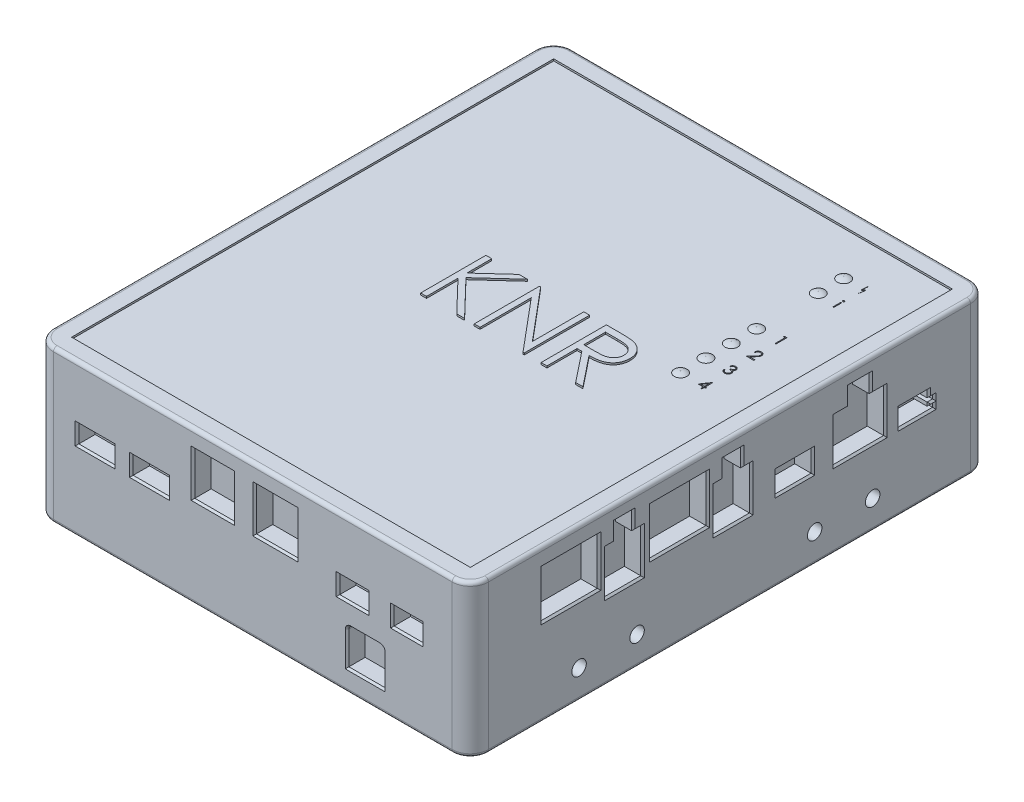
SolidWorks part; units mm, degrees
ref_plane "前基準面" through (0, 0, 0) normal (0, 0, 1) x (1, 0, 0)
ref_plane "上基準面" through (0, 0, 0) normal (0, 1, 0) x (1, 0, 0)
ref_plane "右基準面" through (0, 0, 0) normal (1, 0, 0) x (0, 0, -1)
sketch "草圖1" plane through (0, 0, 0) normal (0, 1, 0) x (1, 0, 0)
  line L1 (0, 0) -> (-120, 0)
  line L2 (0, 0) -> (0, -143)
  line L3 (0, -143) -> (-120, -143)
  line L4 (-120, 0) -> (-120, -143)
  dimension "D1" = 120
  dimension "D2" = 143
extrude "填料-伸長1" add sketch "草圖1" along normal blind 42
fillet "圓角1" radius 5 4 edges at (0, 21, 0) (-120, 21, 0) (-120, 21, 143) (0, 21, 143)
fillet "圓角2" radius 1 16 edges at (-1.4645, 0, 1.4645) (0, 0, 71.5) (-1.4645, 0, 141.5355) (-60, 0, 143) (-118.5355, 0, 141.5355) (-120, 0, 71.5) (-118.5355, 0, 1.4645) (-1.4645, 42, 1.4645) (0, 42, 71.5) (-1.4645, 42, 141.5355) (-60, 42, 143) (-118.5355, 42, 141.5355) (-120, 42, 71.5) (-118.5355, 42, 1.4645) (-60, 0, 0) (-60, 42, 0)
sketch "草圖2" plane through (0, 42, 0) normal (0, 1, 0) x (1, 0, 0)
  line L0 (-115, 0) -> (-5, 0) construction
  line L1 (-115, -5) -> (-5, -5)
  line L2 (-115, -5) -> (-115, -138)
  line L3 (-115, -138) -> (-5, -138)
  line L4 (-5, -5) -> (-5, -138)
  line L5 (-120, -138) -> (-120, -5) construction
  line L6 (0, -5) -> (0, -138) construction
  line L7 (-5, -143) -> (-115, -143) construction
  dimension "D1" = 5
  dimension "D2" = 5
  dimension "D3" = 5
  dimension "D4" = 5
extrude "除料-伸長1" cut sketch "草圖2" against normal blind 0.5
sketch "草圖3" plane through (0, 41.5, 0) normal (0, 1, 0) x (1, 0, 0)
  text T0 "KNR" font "Century Gothic" height 18
extrude "填料-伸長2" add sketch "草圖3" along normal blind 0.5
sketch "草圖4" plane through (0, 41.5, 0) normal (0, 1, 0) x (1, 0, 0)
  line L0 (-5, -138) -> (-5, -5) construction
  line L1 (-5, -5) -> (-115, -5) construction
  circle A0 centre (-23, -17) radius 1.75
  circle A1 centre (-23, -24) radius 1.75
  circle A2 centre (-23, -41) radius 1.75
  circle A3 centre (-23, -48) radius 1.75
  circle A4 centre (-23, -55) radius 1.75
  circle A5 centre (-23, -62) radius 1.75
  dimension "D1" = 18
  dimension "D3" = 3.5
  dimension "D2" = 12
  dimension "D4" = 2
  dimension "D5" = 2
  dimension "D6" = 4
extrude "填料-伸長3" add sketch "草圖4" along normal blind 0.5
fillet "圓角3" radius 3 6 edges at (-23, 42, 18.75) (-23, 42, 63.75) (-23, 42, 56.75) (-23, 42, 49.75) (-23, 42, 42.75) (-23, 42, 25.75)
sketch "草圖6" plane through (0, 41.5, 0) normal (0, 1, 0) x (1, 0, 0)
  circle A0 centre (-23, -17) radius 0.0917 construction
  circle A2 centre (-23, -41) radius 0.0917 construction
  text T0 "ㄣ" font "Century Gothic" height 3
  text T1 "i" font "Century Gothic" height 3
  text T2 "1\r\n2\r\n3\r\n4" font "Century Gothic" height 3
  dimension "D2" = 5
  dimension "D1" = 5
extrude "除料-伸長2" cut sketch "草圖6" against normal blind 0.5
sketch "草圖7" plane through (0, 0, 0) normal (1, 0, 0) x (0, 0, -1)
  line L0 (-143, 1) -> (-143, 41) construction
  line L1 (-123, 37) -> (-107.5, 37)
  line L2 (-123, 37) -> (-123, 24)
  line L3 (-123, 24) -> (-107.5, 24)
  line L4 (-107.5, 37) -> (-107.5, 24)
  line L5 (-138, 42) -> (-5, 42) construction
  line L6 (-105.5, 33) -> (-105.5, 21)
  line L7 (-105.5, 21) -> (-95.5, 21)
  line L8 (-95.5, 21) -> (-95.5, 33)
  line L9 (-95.5, 33) -> (-98, 33)
  line L10 (-98, 33) -> (-98, 38)
  line L11 (-98, 38) -> (-103, 38)
  line L12 (-103, 38) -> (-103, 33)
  line L13 (-103, 33) -> (-105.5, 33)
  line L14 (-93, 24) -> (-77.5, 24)
  line L15 (-93, 37) -> (-93, 24)
  line L16 (-93, 37) -> (-77.5, 37)
  line L17 (-77.5, 37) -> (-77.5, 24)
  line L18 (-75.5, 33) -> (-75.5, 21)
  line L19 (-73, 33) -> (-75.5, 33)
  line L20 (-73, 38) -> (-73, 33)
  line L21 (-68, 38) -> (-73, 38)
  line L22 (-68, 33) -> (-68, 38)
  line L23 (-65.5, 33) -> (-68, 33)
  line L24 (-65.5, 21) -> (-65.5, 33)
  line L25 (-75.5, 21) -> (-65.5, 21)
  line L26 (-42.5, 21) -> (-42.5, 33)
  line L27 (-58.5, 28) -> (-48.5, 28)
  line L28 (-58.5, 28) -> (-58.5, 22)
  line L29 (-58.5, 22) -> (-48.5, 22)
  line L30 (-48.5, 28) -> (-48.5, 22)
  line L31 (-42.5, 33) -> (-38.5, 33)
  line L32 (-38.5, 33) -> (-38.5, 38)
  line L33 (-38.5, 38) -> (-32.5, 38)
  line L34 (-32.5, 38) -> (-32.5, 33)
  line L35 (-32.5, 33) -> (-28.5, 33)
  line L36 (-28.5, 33) -> (-28.5, 21)
  line L37 (-28.5, 21) -> (-42.5, 21)
  line L38 (-16.5, 21) -> (-15, 21)
  line L39 (-24.5, 26) -> (-16.5, 26)
  line L40 (-24.5, 26) -> (-24.5, 21)
  line L41 (-24.5, 21) -> (-16.5, 21)
  line L42 (-16.5, 26) -> (-16.5, 24)
  line L43 (-15, 21) -> (-15, 22)
  line L44 (-15, 22) -> (-16.5, 22)
  line L45 (-15, 24) -> (-16.5, 24)
  line L46 (-15, 23) -> (-15, 24)
  line L47 (-16.5, 23) -> (-15, 23)
  line L48 (-16.5, 23) -> (-16.5, 22)
  dimension "D1" = 20
  dimension "D2" = 5
  dimension "D3" = 13
  dimension "D4" = 15.5
  dimension "D5" = 2
  dimension "D6" = 4
  dimension "D7" = 9
  dimension "D8" = 4.5
  dimension "D9" = 5
  dimension "D10" = 10
  dimension "D11" = 21
  dimension "D12" = 2
  dimension "D13" = 7
  dimension "D14" = 20
  dimension "D15" = 6
  dimension "D16" = 10
  dimension "D17" = 6
  dimension "D18" = 4
  dimension "D19" = 4
  dimension "D20" = 14
  dimension "D21" = 4
  dimension "D22" = 1.5
  dimension "D23" = 1
  dimension "D24" = 8
  dimension "D25" = 5
  dimension "D26" = 2
extrude "除料-伸長3" cut sketch "草圖7" against normal blind 5
chamfer "導角1" distance 0.5 angle 45 46 edges at (0, 26, 20.5) (0, 23.5, 24.5) (0, 25, 16.5) (0, 24, 15.75) (0, 23.5, 15) (0, 23, 15.75) (0, 22.5, 16.5) (0, 22, 15.75) (0, 21.5, 15) (0, 21, 19.75) (0, 21, 35.5) (0, 27, 28.5) (0, 33, 30.5) (0, 35.5, 32.5) (0, 38, 35.5) (0, 35.5, 38.5) (0, 33, 40.5) (0, 27, 42.5) (0, 22, 53.5) (0, 25, 48.5) (0, 28, 53.5) (0, 25, 58.5) (0, 21, 70.5) (0, 27, 65.5) (0, 33, 66.75) (0, 35.5, 68) (0, 38, 70.5) (0, 35.5, 73) (0, 27, 75.5) (0, 33, 74.25) (0, 24, 85.25) (0, 30.5, 77.5) (0, 37, 85.25) (0, 30.5, 93) (0, 33, 96.75) (0, 27, 95.5) (0, 21, 100.5) (0, 35.5, 98) (0, 38, 100.5) (0, 35.5, 103) (0, 33, 104.25) (0, 27, 105.5) (0, 24, 115.25) (0, 30.5, 107.5) (0, 30.5, 123) (0, 37, 115.25)
sketch "草圖8" plane through (0, 0, 0) normal (0, 0, -1) x (-1, 0, 0)
  line L0 (0, 1) -> (0, 41) construction
  line L1 (26, 14) -> (39, 14)
  line L2 (26, 14) -> (26, 8)
  line L3 (26, 8) -> (39, 8)
  line L4 (39, 14) -> (39, 8)
  line L5 (115, 0) -> (5, 0) construction
  line L6 (120, 41) -> (120, 1) construction
  line L7 (23, 25.5) -> (34, 25.5)
  line L8 (23, 25.5) -> (23, 22)
  line L9 (23, 22) -> (34, 22)
  line L10 (34, 25.5) -> (34, 22)
  line L11 (43, 18) -> (55, 18)
  line L12 (43, 18) -> (43, 7)
  line L13 (43, 7) -> (55, 7)
  line L14 (55, 18) -> (55, 7)
  line L15 (59, 18.5) -> (68, 18.5)
  line L16 (59, 18.5) -> (59, 6.5)
  line L17 (59, 6.5) -> (68, 6.5)
  line L18 (68, 18.5) -> (68, 6.5)
  line L19 (37, 20) -> (58, 20)
  line L20 (37, 20) -> (37, 30)
  line L21 (37, 30) -> (58, 30)
  line L22 (58, 20) -> (58, 30)
  line L23 (61, 26.5) -> (68, 26.5)
  line L24 (61, 26.5) -> (61, 21.5)
  line L25 (61, 21.5) -> (68, 21.5)
  line L26 (68, 26.5) -> (68, 21.5)
  line L27 (93, 33) -> (99.5, 33)
  line L28 (93, 33) -> (93, 23)
  line L29 (93, 23) -> (99.5, 23)
  line L30 (99.5, 33) -> (99.5, 23)
  line L31 (5, 42) -> (115, 42) construction
  line L33 (102, 27) -> (108, 27)
  line L34 (102, 27) -> (102, 22)
  line L35 (102, 22) -> (108, 22)
  line L36 (108, 27) -> (108, 22)
  circle A0 centre (79, 11) radius 1.5
  circle A1 centre (76, 23.5) radius 1.5
  dimension "D17" = 3
  dimension "D28" = 3
  dimension "D1" = 26
  dimension "D2" = 13
  dimension "D3" = 8
  dimension "D4" = 6
  dimension "D5" = 23
  dimension "D6" = 11
  dimension "D7" = 3.5
  dimension "D8" = 8
  dimension "D9" = 4
  dimension "D10" = 1
  dimension "D11" = 12
  dimension "D12" = 11
  dimension "D13" = 4
  dimension "D14" = 12
  dimension "D15" = 0.5
  dimension "D16" = 9
  dimension "D18" = 11
  dimension "D19" = 11
  dimension "D20" = 2
  dimension "D21" = 3
  dimension "D22" = 10
  dimension "D23" = 21
  dimension "D24" = 3
  dimension "D25" = 1.5
  dimension "D26" = 5
  dimension "D27" = 7
  dimension "D29" = 8
  dimension "D30" = 2
  dimension "D31" = 27
  dimension "D32" = 19
  dimension "D33" = 6.5
  dimension "D34" = 10
  dimension "D35" = 2.5
  dimension "D36" = 1
  dimension "D37" = 5
  dimension "D38" = 6
extrude "除料-伸長4" cut sketch "草圖8" against normal blind 5
sketch "草圖10" plane through (0, 0, 5) normal (0, 0, -1) x (-1, 0, 0)
  circle A0 centre (76, 23.5) radius 1.5
extrude "填料-伸長4" add sketch "草圖10" along normal blind 6
fillet "圓角4" radius 1.5 1 edges at (-77.5, 23.5, -1)
chamfer "導角2" distance 0.8 angle 45 33 edges at (-28.5, 25.5, 0) (-105, 22, 0) (-108, 24.5, 0) (-105, 27, 0) (-102, 24.5, 0) (-96.25, 33, 0) (-93, 28, 0) (-99.5, 28, 0) (-96.25, 23, 0) (-80.5, 11, 0) (-68, 24, 0) (-64.5, 26.5, 0) (-61, 24, 0) (-64.5, 21.5, 0) (-63.5, 6.5, 0) (-59, 12.5, 0) (-68, 12.5, 0) (-63.5, 18.5, 0) (-26, 11, 0) (-32.5, 14, 0) (-39, 11, 0) (-32.5, 8, 0) (-49, 7, 0) (-43, 12.5, 0) (-55, 12.5, 0) (-49, 18, 0) (-58, 25, 0) (-47.5, 20, 0) (-37, 25, 0) (-47.5, 30, 0) (-34, 23.75, 0) (-28.5, 22, 0) (-23, 23.75, 0)
sketch "草圖11" plane through (-120, 0, 0) normal (-1, 0, 0) x (0, 0, 1)
  line L0 (0, 1) -> (0, 41) construction
  line L1 (20, 34) -> (56, 34)
  line L2 (20, 34) -> (20, 22)
  line L3 (20, 22) -> (56, 22)
  line L4 (56, 34) -> (56, 22)
  line L5 (5, 42) -> (138, 42) construction
  line L6 (105, 24) -> (105, 37)
  line L7 (59, 22.5) -> (71, 22.5)
  line L8 (59, 22.5) -> (59, 28)
  line L9 (59, 28) -> (71, 28)
  line L10 (71, 22.5) -> (71, 28)
  line L11 (75, 37) -> (90.5, 37)
  line L12 (105, 37) -> (120.5, 37)
  line L13 (120.5, 37) -> (120.5, 24)
  line L14 (120.5, 24) -> (105, 24)
  line L15 (90.5, 37) -> (90.5, 24)
  line L16 (90.5, 24) -> (75, 24)
  line L17 (75, 24) -> (75, 37)
  line L18 (123, 33) -> (123, 21)
  line L19 (123, 21) -> (133, 21)
  line L20 (133, 21) -> (133, 33)
  line L21 (133, 33) -> (130.5, 33)
  line L22 (130.5, 33) -> (130.5, 38)
  line L23 (125.5, 38) -> (125.5, 33)
  line L24 (125.5, 33) -> (123, 33)
  line L25 (130.5, 38) -> (125.5, 38)
  line L34 (103, 33) -> (100.5, 33)
  line L35 (103, 21) -> (103, 33)
  line L36 (93, 21) -> (103, 21)
  line L37 (93, 33) -> (93, 21)
  line L38 (95.5, 33) -> (93, 33)
  line L39 (95.5, 38) -> (95.5, 33)
  line L40 (100.5, 38) -> (95.5, 38)
  line L41 (100.5, 33) -> (100.5, 38)
  dimension "D1" = 20
  dimension "D2" = 20
  dimension "D3" = 12
  dimension "D4" = 36
  dimension "D5" = 5.5
  dimension "D6" = 0.5
  dimension "D7" = 3
  dimension "D8" = 12
  dimension "D9" = 4
  dimension "D10" = 15.5
  dimension "D11" = 13
  dimension "D12" = 18
  dimension "D13" = 2.5
  dimension "D14" = 12
  dimension "D15" = 5
  dimension "D16" = 2.5
  dimension "D17" = 9
  dimension "D18" = 4
  dimension "D19" = 10
  dimension "D20" = 2
extrude "除料-伸長5" cut sketch "草圖11" against normal blind 5
sketch "草圖13" plane through (0, 0, 143) normal (0, 0, 1) x (1, 0, 0)
  line L0 (-115, 42) -> (-5, 42) construction
  line L1 (-108.5, 27) -> (-98.5, 27)
  line L2 (-108.5, 27) -> (-108.5, 22)
  line L3 (-108.5, 22) -> (-98.5, 22)
  line L4 (-98.5, 27) -> (-98.5, 22)
  line L5 (-120, 1) -> (-120, 41) construction
  line L6 (-93.5, 27) -> (-83.5, 27)
  line L7 (-93.5, 27) -> (-93.5, 22)
  line L8 (-83.5, 27) -> (-83.5, 22)
  line L9 (-93.5, 22) -> (-83.5, 22)
  line L10 (-59.5, 37) -> (-59.5, 25)
  line L11 (-76.5, 37) -> (-65.5, 37)
  line L12 (-76.5, 37) -> (-76.5, 25)
  line L13 (-76.5, 25) -> (-65.5, 25)
  line L14 (-65.5, 37) -> (-65.5, 25)
  line L15 (-59.5, 37) -> (-48, 37)
  line L16 (-59.5, 25) -> (-48, 25)
  line L17 (-48, 25) -> (-48, 37)
  line L18 (-36.5, 27) -> (-28.5, 27)
  line L19 (-21.5, 27) -> (-13.5, 27)
  line L20 (-21.5, 27) -> (-21.5, 22)
  line L21 (-21.5, 22) -> (-13.5, 22)
  line L22 (-13.5, 27) -> (-13.5, 22)
  line L23 (-36.5, 27) -> (-36.5, 22)
  line L24 (-28.5, 27) -> (-28.5, 22)
  line L25 (-36.5, 22) -> (-28.5, 22)
  line L26 (-5, 0) -> (-115, 0) construction
  line L27 (-33, 16) -> (-25, 16)
  line L28 (-34, 15) -> (-34, 6)
  line L29 (-34, 6) -> (-24, 6)
  line L30 (-24, 15) -> (-24, 6)
  line L31 (0, 41) -> (0, 1) construction
  arc A0 (-25, 16) -> (-24, 15) centre (-25, 15) cw
  arc A1 (-33, 16) -> (-34, 15) centre (-33, 15) ccw
  point P39 (-24, 16)
  point P42 (-34, 16)
  dimension "D24" = 1
  dimension "D1" = 10
  dimension "D2" = 20
  dimension "D3" = 11.5
  dimension "D4" = 5
  dimension "D6" = 7
  dimension "D7" = 5
  dimension "D8" = 17
  dimension "D9" = 11
  dimension "D10" = 12
  dimension "D12" = 6
  dimension "D13" = 5
  dimension "D11" = 12
  dimension "D14" = 11.5
  dimension "D15" = 21.5
  dimension "D16" = 8
  dimension "D17" = 20
  dimension "D18" = 5
  dimension "D20" = 6
  dimension "D21" = 10
  dimension "D22" = 34
  dimension "D23" = 10
  dimension "D5" = 2
  dimension "D19" = 2
extrude "除料-伸長6" cut sketch "草圖13" against normal blind 5
chamfer "導角3" distance 0.5 angle 45 30 edges at (-29, 6, 143) (-24, 10.5, 143) (-24.2929, 15.7071, 143) (-29, 16, 143) (-33.7071, 15.7071, 143) (-34, 10.5, 143) (-17.5, 22, 143) (-13.5, 24.5, 143) (-17.5, 27, 143) (-21.5, 24.5, 143) (-28.5, 24.5, 143) (-32.5, 27, 143) (-36.5, 24.5, 143) (-32.5, 22, 143) (-53.75, 25, 143) (-48, 31, 143) (-53.75, 37, 143) (-59.5, 31, 143) (-71, 37, 143) (-65.5, 31, 143) (-76.5, 31, 143) (-71, 25, 143) (-83.5, 24.5, 143) (-88.5, 27, 143) (-93.5, 24.5, 143) (-88.5, 22, 143) (-98.5, 24.5, 143) (-103.5, 27, 143) (-108.5, 24.5, 143) (-103.5, 22, 143)
sketch "草圖14" plane through (-120, 0, 0) normal (-1, 0, 0) x (0, 0, 1)
  line L0 (138, 0) -> (5, 0) construction
  line L1 (0, 1) -> (0, 41) construction
  circle A0 centre (32, 8) radius 2
  circle A1 centre (48, 8) radius 2
  circle A2 centre (97, 8) radius 2
  circle A3 centre (113, 8) radius 2
  dimension "D1" = 8
  dimension "D3" = 4
  dimension "D2" = 32
  dimension "D4" = 2
  dimension "D5" = 2
extrude "除料-伸長7" cut sketch "草圖14" against normal blind 5
sketch "草圖15" plane through (0, 0, 0) normal (1, 0, 0) x (0, 0, -1)
  circle A0 centre (-32, 8) radius 2 construction
  circle A1 centre (-32, 8) radius 2
  circle A2 centre (-48, 8) radius 2 construction
  circle A3 centre (-48, 8) radius 2
  circle A5 centre (-97, 8) radius 2
  circle A6 centre (-97, 8) radius 2
  circle A7 centre (-113, 8) radius 2
  circle A8 centre (-113, 8) radius 2
  dimension "D1" = 0
  dimension "D2" = 0
extrude "除料-伸長8" cut sketch "草圖15" against normal blind 5
sketch "草圖16" plane through (0, 0, 0) normal (0, -1, 0) x (1, 0, 0)
  line L0 (0, 138) -> (0, 5) construction
  line L2 (-115, 143) -> (-5, 143) construction
  line L4 (-120, 5) -> (-120, 138) construction
  circle A0 centre (-8, 113) radius 2
  circle A1 centre (-8, 97) radius 2
  circle A2 centre (-112, 97) radius 2
  circle A3 centre (-112, 113) radius 2
  circle A4 centre (-112, 33) radius 2
  circle A5 centre (-112, 49) radius 2
  circle A6 centre (-8, 33) radius 2
  circle A7 centre (-8, 49) radius 2
  circle A8 centre (-81, 135) radius 2
  circle A9 centre (-65, 135) radius 2
  circle A10 centre (-49, 135) radius 2
  circle A11 centre (-33, 135) radius 2
  dimension "D1" = 4
  dimension "D9" = 4
  dimension "D2" = 8
  dimension "D3" = 30
  dimension "D7" = 8
  dimension "D8" = 39
  dimension "D4" = 2
  dimension "D5" = 2
  dimension "D6" = 2
  dimension "D10" = 2
  dimension "D11" = 2
extrude "除料-伸長9" cut sketch "草圖16" against normal blind 5
